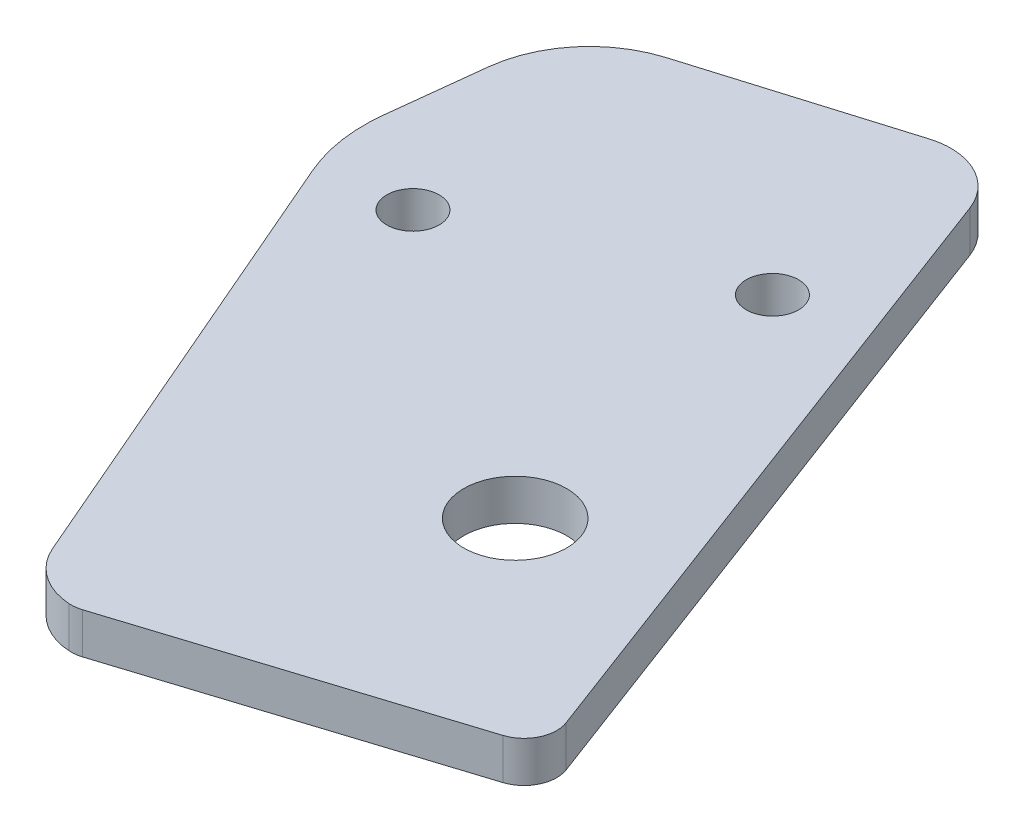
SolidWorks part; units mm, degrees
ref_plane "Front Plane" through (0, 0, 0) normal (0, 0, 1) x (1, 0, 0)
ref_plane "Top Plane" through (0, 0, 0) normal (0, 1, 0) x (1, 0, 0)
ref_plane "Right Plane" through (0, 0, 0) normal (1, 0, 0) x (0, 0, -1)
sketch "Sketch1" plane through (0, 0, 0) normal (0, 1, 0) x (1, 0, 0)
  line L0 (12.7, -6.35) -> (25.4, -6.35)
  line L1 (-12.7, -19.05) -> (12.7, -19.05)
  line L2 (-12.7, -19.05) -> (-12.7, 19.05)
  line L3 (-12.7, 19.05) -> (12.7, 19.05)
  line L4 (12.7, -19.05) -> (12.7, 19.05)
  line L5 (-12.7, -19.05) -> (12.7, 19.05) construction
  line L6 (-12.7, 19.05) -> (12.7, -19.05) construction
  line L7 (25.4, -6.35) -> (25.4, -19.05)
  line L8 (25.4, -19.05) -> (12.7, -19.05)
  point P0 (0, 0)
  dimension "D1" = 25.4
  dimension "D2" = 38.1
  dimension "D3" = 12.7
  dimension "D4" = 12.7
extrude "Boss-Extrude1" add sketch "Sketch1" along normal blind 3.175 contours L1 L4 L3 L2 | L8 L7 L0 L4 region at (19.05, 0, 12.7) region at (0, 0, 0)
sketch "Sketch2" plane through (0, 0, 0) normal (0, -1, 0) x (1, 0, 0)
  line L0 (37.3484, -5.4015) -> (58.4225, -30.0473) construction
  line L1 (58.4225, -30.0473) -> (56.4244, -36.6557) construction
  line L2 (56.4244, -36.6557) -> (28.4937, -28.211) construction
  line L3 (27.672, -14.5925) -> (16.8921, 0.2466) construction
  line L4 (18.9846, 3.1897) -> (28.6818, 0.2578) construction
  line L5 (-33.4925, -38.7551) -> (-34.3249, -31.4398) construction
  line L6 (-33.4148, -25.2954) -> (-18.0647, 10.2749) construction
  line L7 (-1.2058, -33.65) -> (-6.5286, -47.7836) construction
  line L8 (-11.9748, -50.4718) -> (-27.6795, -45.7236) construction
  line L9 (37.3484, -5.4015) -> (58.4225, -30.0473)
  line L10 (58.4225, -30.0473) -> (56.4244, -36.6557)
  line L11 (56.4244, -36.6557) -> (28.4937, -28.211)
  line L12 (27.672, -14.5925) -> (16.8921, 0.2466)
  line L13 (18.9846, 3.1897) -> (28.6818, 0.2578)
  line L14 (-33.4925, -38.7551) -> (-34.3249, -31.4398)
  line L15 (-33.4148, -25.2954) -> (-18.0647, 10.2749)
  line L16 (-1.2058, -33.65) -> (-6.5286, -47.7836)
  line L17 (-11.9748, -50.4718) -> (-27.6795, -45.7236)
  line L18 (-13.3731, 13.4695) -> (19.0101, 3.1818)
  line L20 (-25.2482, -46.4587) -> (-27.4348, -26.2567) construction
  line L21 (-13.0917, -50.1342) -> (-7.7649, -34.5071) construction
  line L22 (-34.9558, -31.5116) -> (-34.1234, -38.8269) construction
  line L23 (-27.8633, -46.3314) -> (-12.1585, -51.0797) construction
  line L24 (-5.9343, -48.0074) -> (-0.6115, -33.8738) construction
  line L25 (-18.6477, 10.5265) -> (-33.9978, -25.0438) construction
  line L26 (-34.9558, -31.5116) -> (-34.1234, -38.8269)
  line L27 (-27.8633, -46.3314) -> (-12.1585, -51.0797)
  line L28 (-5.9343, -48.0074) -> (-0.6115, -33.8738)
  line L29 (-18.6477, 10.5265) -> (-33.9978, -25.0438)
  line L31 (-0.6115, -33.8738) -> (13.9492, 4.7896)
  arc A0 (37.3484, -5.4015) -> (28.6818, 0.2578) centre (23.3524, -17.3692) ccw construction
  arc A1 (27.5335, -25.2281) -> (28.4937, -28.211) centre (29.045, -26.3876) ccw construction
  arc A2 (27.5335, -25.2281) -> (27.672, -14.5925) centre (20.4796, -19.8175) ccw construction
  arc A3 (18.9846, 3.1897) -> (16.8921, 0.2466) centre (18.4333, 1.3662) ccw construction
  arc A4 (-33.4925, -38.7551) -> (-27.6795, -45.7236) centre (-25.2904, -37.8219) ccw construction
  arc A5 (-33.4148, -25.2954) -> (-34.3249, -31.4398) centre (-22.3372, -30.0758) ccw construction
  arc A6 (-14.2611, 12.95) -> (-18.0647, 10.2749) centre (-13.9835, 8.5137) ccw construction
  arc A7 (-13.2163, 9.3838) -> (-14.2611, 12.95) centre (-14.1421, 11.0487) ccw construction
  arc A8 (-13.2163, 9.3838) -> (-2.9671, -31.0738) centre (-2.7239, -9.4851) ccw construction
  arc A9 (-1.2058, -33.65) -> (-2.9671, -31.0738) centre (-2.9886, -32.9786) ccw construction
  arc A10 (-11.9748, -50.4718) -> (-6.5286, -47.7836) centre (-10.6883, -46.2171) ccw construction
  arc A11 (37.3484, -5.4015) -> (28.6818, 0.2578) centre (23.3524, -17.3692) ccw
  arc A12 (27.5335, -25.2281) -> (28.4937, -28.211) centre (29.045, -26.3876) ccw
  arc A13 (27.5335, -25.2281) -> (27.672, -14.5925) centre (20.4796, -19.8175) ccw
  arc A14 (18.9846, 3.1897) -> (16.8921, 0.2466) centre (18.4333, 1.3662) ccw
  arc A15 (-33.4925, -38.7551) -> (-27.6795, -45.7236) centre (-25.2904, -37.8219) ccw
  arc A16 (-33.4148, -25.2954) -> (-34.3249, -31.4398) centre (-22.3372, -30.0758) ccw
  arc A17 (-14.2611, 12.95) -> (-18.0647, 10.2749) centre (-13.9835, 8.5137) ccw
  arc A18 (-13.2163, 9.3838) -> (-14.2611, 12.95) centre (-14.1421, 11.0487) ccw
  arc A19 (-13.2163, 9.3838) -> (-2.9671, -31.0738) centre (-2.7239, -9.4851) ccw
  arc A20 (-1.2058, -33.65) -> (-2.9671, -31.0738) centre (-2.9886, -32.9786) ccw
  arc A21 (-11.9748, -50.4718) -> (-6.5286, -47.7836) centre (-10.6883, -46.2171) ccw
  circle A22 centre (-2.7239, -9.4851) radius 4
  circle A23 centre (-7.7649, -34.5071) radius 2.032
  circle A24 centre (-27.4348, -26.2567) radius 2.032
  arc A25 (-34.1234, -38.8269) -> (-27.8633, -46.3314) centre (-25.2904, -37.8219) ccw construction
  arc A26 (-12.1585, -51.0797) -> (-5.9343, -48.0074) centre (-10.6883, -46.2171) ccw construction
  arc A27 (-0.6115, -33.8738) -> (-2.96, -30.4388) centre (-2.9886, -32.9786) ccw construction
  arc A28 (-12.9077, 8.8289) -> (-14.3007, 13.5838) centre (-14.1421, 11.0487) ccw construction
  arc A29 (-14.3007, 13.5838) -> (-18.6477, 10.5265) centre (-13.9835, 8.5137) ccw construction
  arc A30 (-33.9978, -25.0438) -> (-34.9558, -31.5116) centre (-22.3372, -30.0758) ccw construction
  arc A31 (-34.1234, -38.8269) -> (-27.8633, -46.3314) centre (-25.2904, -37.8219) ccw
  arc A32 (-12.1585, -51.0797) -> (-5.9343, -48.0074) centre (-10.6883, -46.2171) ccw
  arc A33 (-0.6115, -33.8738) -> (-2.96, -30.4388) centre (-2.9886, -32.9786) ccw
  arc A34 (-12.9077, 8.8289) -> (-14.3007, 13.5838) centre (-14.1421, 11.0487) ccw
  arc A35 (-14.3007, 13.5838) -> (-18.6477, 10.5265) centre (-13.9835, 8.5137) ccw
  arc A36 (-33.9978, -25.0438) -> (-34.9558, -31.5116) centre (-22.3372, -30.0758) ccw
  line M1 (25.4, 19.05) -> (-12.7, 19.05)
  line M2 (-12.7, 19.05) -> (-12.7, -19.05)
  line M3 (-12.7, -19.05) -> (12.7, -19.05)
  line M4 (12.7, -19.05) -> (12.7, 6.35)
  line M5 (12.7, 6.35) -> (25.4, 6.35)
  line M6 (25.4, 6.35) -> (25.4, 19.05)
  dimension "D1" = 8
  dimension "D8" = 4.064
  dimension "D2" = 15.24
  dimension "D3" = 16.51
  dimension "D4" = 20.32
  dimension "D5" = 2.54
  dimension "D6" = 67
  dimension "D7" = 92
extrude "Boss-Extrude2" add sketch "Sketch2" against normal blind 3.175 contours L17 A21 L16 A20 A19 A17 L15 A16 L14 A15 M3 M2 | A19 M2 | A20 A19 M3 | L29 A36 L26 A31 L27 A32 L28 A33 A20 L16 A21 L17 A15 L14 A16 L15 A17 A18 A34 A35 M2 | A34 L18 M2 | L31 L18 M4 M5 region at (13.1164, 0, 3.8162) region at (-12.865, 0, 13.2738) region at (-13.8893, 0, -16.3603) region at (-19.8862, 0, -32.0856)
extrude "Cut-Extrude1" cut sketch "Sketch2<3>" against normal through all contours L18 M2 M5 M6 M1 | L31 M3 M4 | A22 region at (8.5325, 0, 13.4044) region at (10.1237, 0, -12.2091) region at (-2.7239, 0, -9.4851)
sketch "Sketch2<3>" plane through (0, 0, 0) normal (0, -1, 0) x (1, 0, 0) same geometry as "Sketch2"
fillet "Fillet1" radius 2.54 1 edges at (13.9492, 1.5875, 4.7896)
